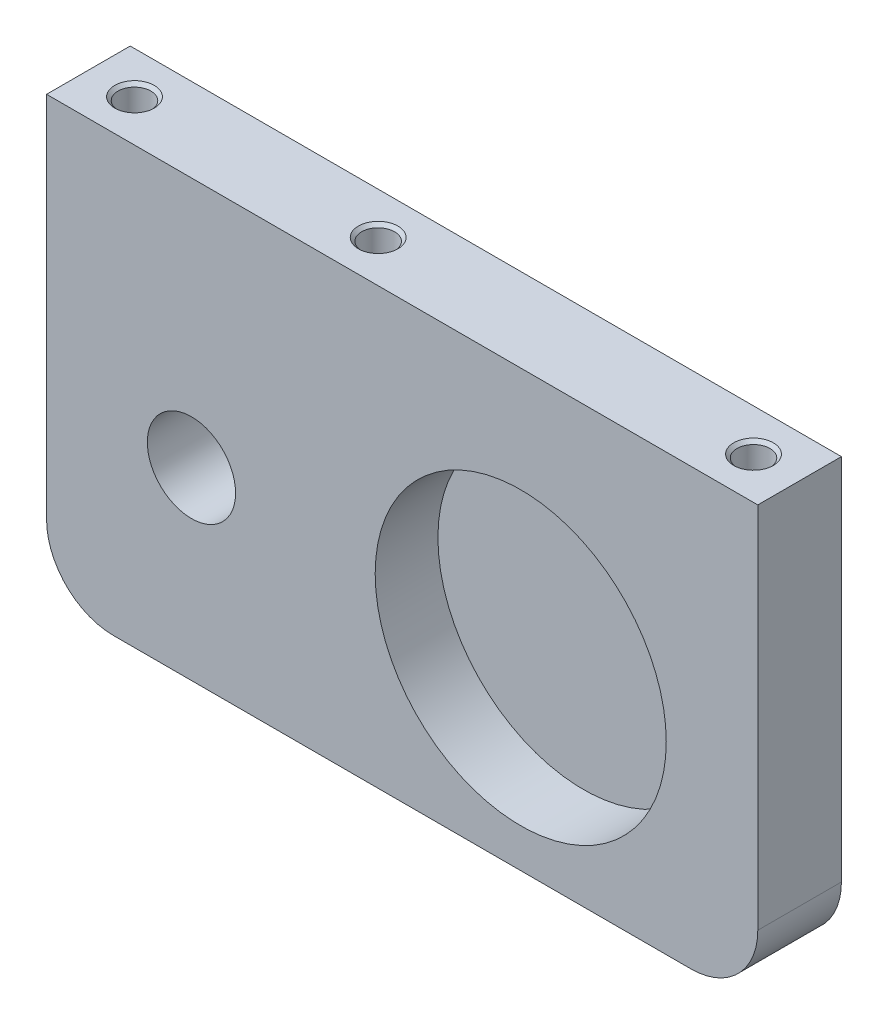
SolidWorks part; units mm, degrees
ref_plane "Front Plane" through (0, 0, 0) normal (0, 0, 1) x (1, 0, 0)
ref_plane "Top Plane" through (0, 0, 0) normal (0, 1, 0) x (1, 0, 0)
ref_plane "Right Plane" through (0, 0, 0) normal (1, 0, 0) x (0, 0, -1)
sketch "Sketch1" plane through (0, 0, 0) normal (0, 0, 1) x (1, 0, 0)
  line L10 (-36, 19.05) -> (18, 19.05)
  line L11 (-36, 19.05) -> (-36, -14)
  line L12 (-36, -14) -> (18, -14)
  line L13 (18, 19.05) -> (18, -14)
  circle A2 centre (0, 0) radius 11.05 construction
  circle A3 centre (-25, 0) radius 3.35 construction
  point P4 (0, 0)
  point P6 (0, 0)
  point P10 (0, 0)
  point P11 (0, 0)
  dimension "D2" = 6.7
  dimension "D5" = 19.05
  dimension "D6" = 11
  dimension "D3" = 25
  dimension "D1" = 22.1
  dimension "D4" = 14
  dimension "D7" = 18
extrude "Boss-Extrude1" add sketch "Sketch1" against normal blind 6.35
sketch "Sketch8" plane through (0, 19.05, 0) normal (0, 1, 0) x (1, 0, 0)
  line L0 (-36, 3.175) -> (18, 3.175) construction
  line L1 (-36, 6.35) -> (-36, 0) construction
  line L2 (18, 6.35) -> (18, 0) construction
  circle A1 centre (-32.5, 3.175) radius 1.25
  circle A2 centre (-14, 3.175) radius 1.25
  circle A3 centre (14.5, 3.175) radius 1.25
  dimension "D1" = 2.5
  dimension "D2" = 3.5
  dimension "D3" = 3.5
  dimension "D4" = 14
extrude "Cut-Extrude4" cut sketch "Sketch8" against normal blind 15
sketch "Sketch10" plane through (0, 0, 0) normal (0, 0, 1) x (1, 0, 0)
  circle A0 centre (-25, 0) radius 3.35 construction
  circle A1 centre (0, 0) radius 11.05 construction
  circle A2 centre (-25, 0) radius 3.35
  circle A3 centre (0, 0) radius 11.05
extrude "Cut-Extrude5" cut sketch "Sketch10" against normal offset from surface (4.7625 mm away) 1.5875 up to face at (-9, 2.525, -6.35)
fillet "Fillet3" radius 5.08 2 edges at (18, -14, -3.175) (-36, -14, -3.175)
chamfer "Chamfer1" distance 0.25 angle 45 3 edges at (14.5, 19.05, -1.925) (-14, 19.05, -1.925) (-32.5, 19.05, -1.925)
